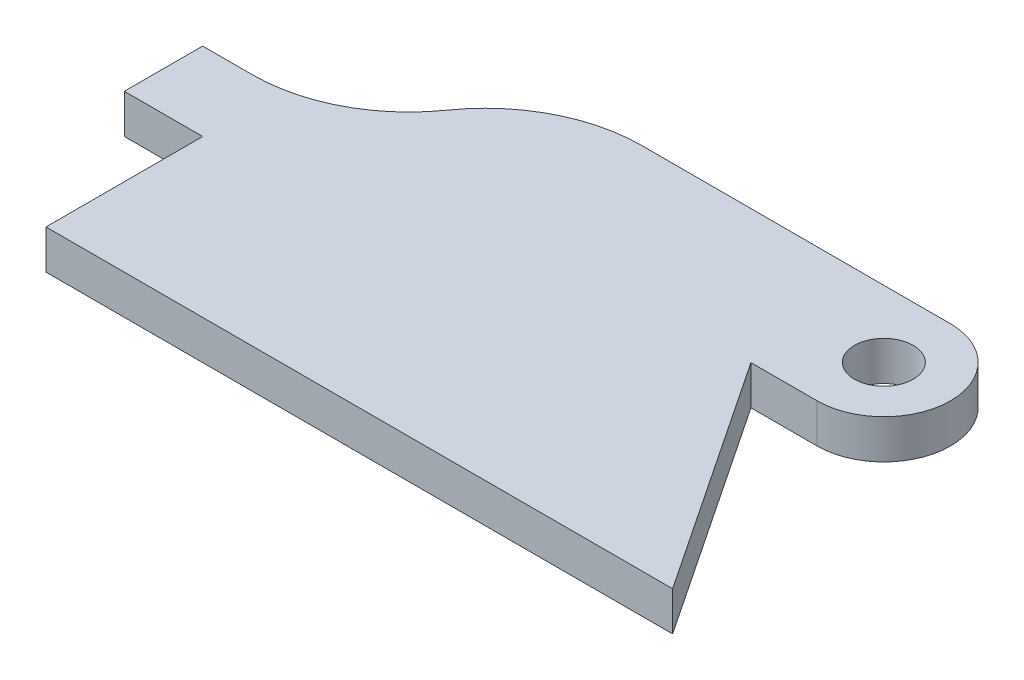
SolidWorks part; units mm, degrees
material "AISI Type A2 Tool Steel"
ref_plane "Front Plane" through (0, 0, 0) normal (0, 0, 1) x (1, 0, 0)
ref_plane "Top Plane" through (0, 0, 0) normal (0, 1, 0) x (1, 0, 0)
ref_plane "Right Plane" through (0, 0, 0) normal (1, 0, 0) x (0, 0, -1)
other "Bounding Box"
ref_plane "Default Plane" through (-8.9266, -12.7485, 0) normal (-0.1736, 0.9848, 0) x (0.9848, 0.1736, 0)
sketch "Sketch1" plane through (0, 0, 0) normal (0, 1, 0) x (1, 0, 0)
  line L0 (0, 0) -> (33.1415, 0)
  line L1 (88.9, 0) -> (114.3, -38.1)
  line L2 (114.3, -38.1) -> (12.7, -38.1)
  line L3 (12.7, -38.1) -> (12.7, -12.7)
  line L4 (12.7, -12.7) -> (0, -12.7)
  line L5 (0, -12.7) -> (0, 0)
  line L6 (99.6289, 0) -> (88.9, 0)
  line L7 (33.1415, 21.632) -> (33.1415, 0)
  line L9 (99.6289, 21.632) -> (33.1415, 21.632)
  circle A0 centre (99.6289, 10.816) radius 4.7625
  arc A1 (99.6289, 21.632) -> (99.6289, 0) centre (99.6289, 10.816) cw
  point P10 (61.9802, 14.3552)
  point P13 (66.3805, 14.0512)
  point P14 (62.2838, 21.5321)
  point P15 (0, 0)
  point P16 (76.2, 7.62)
  point P17 (62.3847, 21.4353)
  point P19 (76.2, 7.62)
  point P20 (76.2, 7.5756)
  point P21 (76.2, 9.6141)
  point P22 (76.2, 9.5064)
  point P23 (76.2, 9.5578)
  point P24 (64.8731, 21.5584)
  point P25 (76.2, 10.0731)
  point P26 (33.1415, 21.632)
  point P27 (76.2, 0)
  point P28 (76.2, 9.9995)
  point P29 (84.447, 0)
  point P30 (98.0411, -0.6022)
  point P31 (86.9289, 0)
  point P32 (0, 0)
  dimension "D8" = 9.525
  dimension "D9" = 10.7289
  dimension "D6" = 10.816
  dimension "D1" = 12.7
  dimension "D2" = 38.1
  dimension "D3" = 101.6
  dimension "D4" = 88.9
  dimension "D5" = 12.7
  dimension "D10" = 33.1415
extrude "Boss-Extrude1" add sketch "Sketch1" along normal blind 6.35
fillet "Fillet1" radius 25.4 1 edges at (33.1415, 3.175, 0)
fillet "Fillet2" radius 25.4 1 edges at (33.1415, 3.175, -21.632)
sketch "Sketch2" plane through (0, 6.35, 0) normal (0, 1, 0) x (1, 0, 0)
